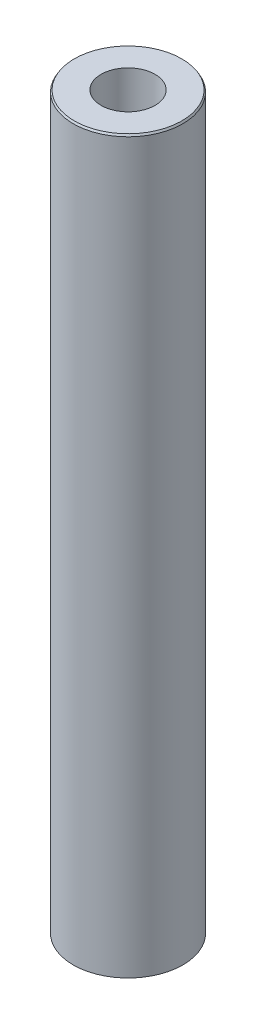
SolidWorks part; units mm, degrees
ref_plane "Front Plane" through (0, 0, 0) normal (0, 0, 1) x (1, 0, 0)
ref_plane "Top Plane" through (0, 0, 0) normal (0, 1, 0) x (1, 0, 0)
ref_plane "Right Plane" through (0, 0, 0) normal (1, 0, 0) x (0, 0, -1)
sketch "Sketch1" plane through (0, 0, 0) normal (0, 1, 0) x (1, 0, 0)
  circle A0 centre (0, 0) radius 45
  dimension "SHAFT_OD" = 90
extrude "Boss-Extrude1" add sketch "Sketch1" along normal blind 600
sketch "Sketch2" plane through (0, 0, 0) normal (0, 1, 0) x (1, 0, 0)
  circle A0 centre (0, 0) radius 22.1218
  dimension "BORE_D" = 44.2435
extrude "Cut-Extrude1" cut sketch "Sketch2" along normal through all
chamfer "Chamfer1" distance 1.55 angle 30 2 edges at (0, 600, 45) (0, 0, 45) first distance on face at (0, 600, 45) first distance on face at (0, 0, 22.1218)
